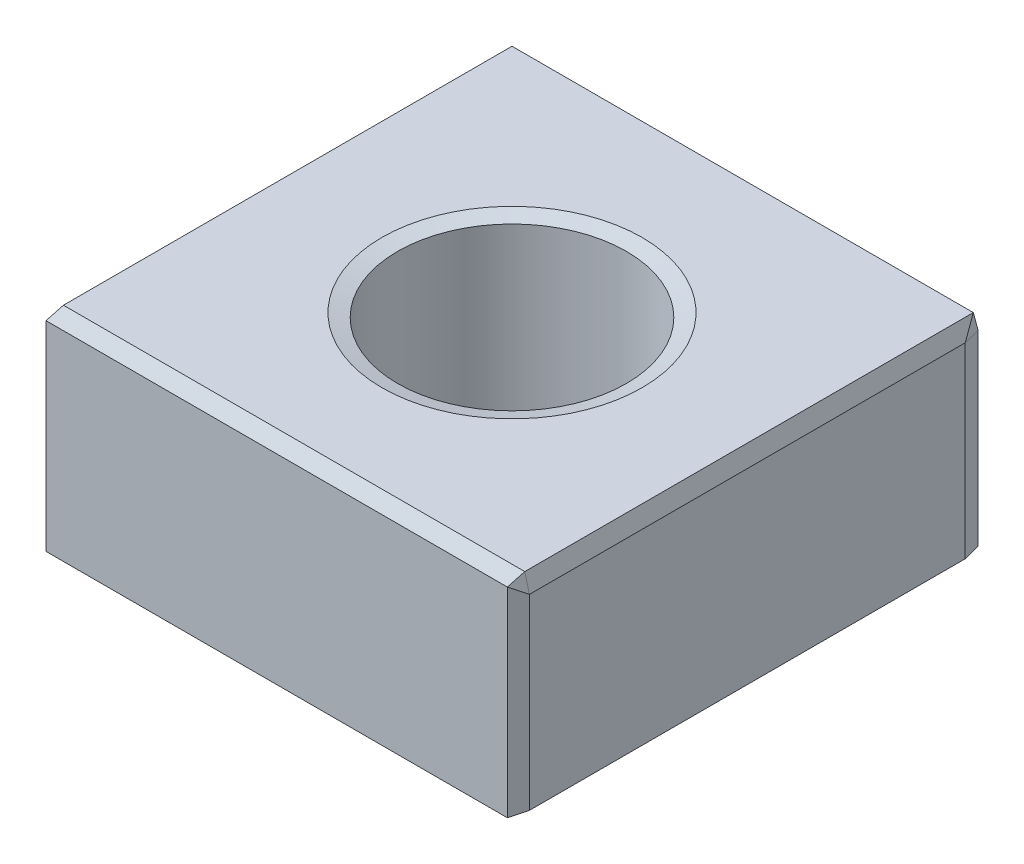
SolidWorks part; units mm, degrees
ref_plane "Front Plane" through (0, 0, 0) normal (0, 0, 1) x (1, 0, 0)
ref_plane "Top Plane" through (0, 0, 0) normal (0, 1, 0) x (1, 0, 0)
ref_plane "Right Plane" through (0, 0, 0) normal (1, 0, 0) x (0, 0, -1)
sketch "Sketch1" plane through (0, 0, 0) normal (0, 1, 0) x (1, 0, 0)
  line L1 (27, -27) -> (-27, -27)
  line L2 (27, -27) -> (27, 27)
  line L3 (27, 27) -> (-27, 27)
  line L4 (-27, -27) -> (-27, 27)
  line L5 (27, -27) -> (-27, 27) construction
  line L6 (27, 27) -> (-27, -27) construction
  point P0 (0, 0)
  dimension "D1" = 54
extrude "Boss-Extrude1" add sketch "Sketch1" along normal blind 24
chamfer "Chamfer1" distance 2 angle 15 12 edges at (-27, 24, 0) (-27, 0, 0) (0, 24, -27) (-27, 12, -27) (0, 0, -27) (27, 24, 0) (27, 12, -27) (27, 0, 0) (-27, 12, 27) (0, 24, 27) (27, 12, 27) (0, 0, 27)
hole_wizard "M24 Clearance Hole1" positions "Sketch2" profile "Sketch3" hole size "M24" standard "ANSI Metric"
sketch "Sketch2" plane through (0, 24, 0) normal (0, 1, 0) x (1, 0, 0)
  point P0 (0, 0)
sketch "Sketch3" plane through (0, 24, 0) normal (1, 0, 0) x (0, 0, 1)
  line L0 (0, 0) -> (0, 24)
  line L1 (0, 24) -> (13.13, 24)
  line L2 (13.13, 24) -> (13.13, 0)
  line L5 (13.13, 0) -> (0, 0)
  line L10 (0, 24) -> (-13.13, 24) construction
  line L11 (0, -6.35) -> (0, 107.95) construction
  dimension "Hole Dia." = 26.26
  dimension "Hole Depth" = 24
  dimension "Drill Angle" = 180
chamfer "Chamfer2" distance 1.8 angle 15 2 edges at (0, 24, 13.13) (0, 0, 13.13)
